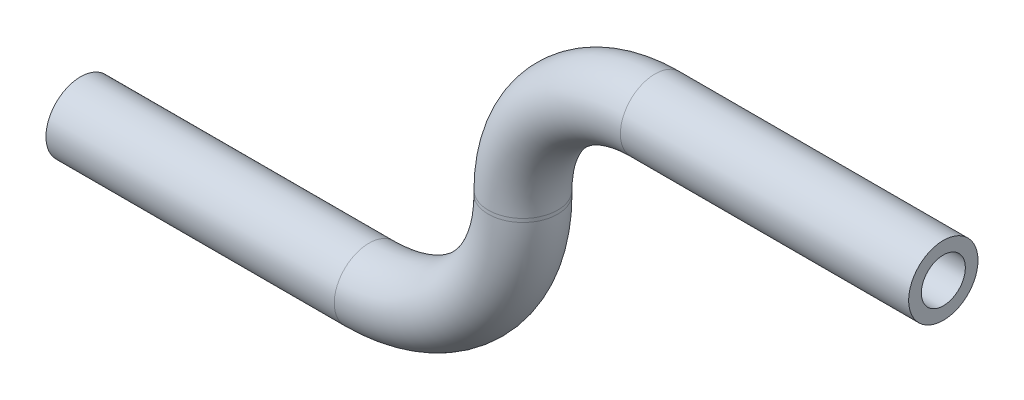
SolidWorks part; units mm, degrees
material "PE High Density"
ref_plane "Front" through (0, 0, 0) normal (0, 0, 1) x (1, 0, 0)
ref_plane "Top" through (0, 0, 0) normal (0, 1, 0) x (1, 0, 0)
ref_plane "Right" through (0, 0, 0) normal (1, 0, 0) x (0, 0, -1)
ref_axis "Axis1" through (0, 0, 55) along (0, 0, -1)
sketch "Sketch1" plane through (0, 0, 0) normal (0, 0, 1) x (1, 0, 0)
  line L0 (0, 0) -> (33.274, 0)
  line L1 (51.054, 17.78) -> (51.054, 18.1864)
  line L2 (66.294, 33.4264) -> (99.568, 33.4264)
  arc A0 (51.054, 18.1864) -> (66.294, 33.4264) centre (66.294, 18.1864) cw
  arc A1 (33.274, 0) -> (51.054, 17.78) centre (33.274, 17.78) ccw
  point P7 (51.054, 33.4264)
  point P10 (51.054, 0)
  dimension "D3" = 15.24
  dimension "D4" = 17.78
  dimension "D1" = 33.4264
  dimension "D2" = 99.568
ref_plane "Plane1" through (99.568, 33.4264, 0) normal (1, 0, 0) x (0, 0, -1)
sketch "Sketch2" plane through (99.568, 33.4264, 0) normal (1, 0, 0) x (0, 0, -1)
  circle A0 centre (0, 0) radius 2.54
  circle A1 centre (0, 0) radius 4
  dimension "D1" = 8
  dimension "D2" = 5.08
sweep "Sweep1" add profiles "Sketch2" path "Sketch1"
